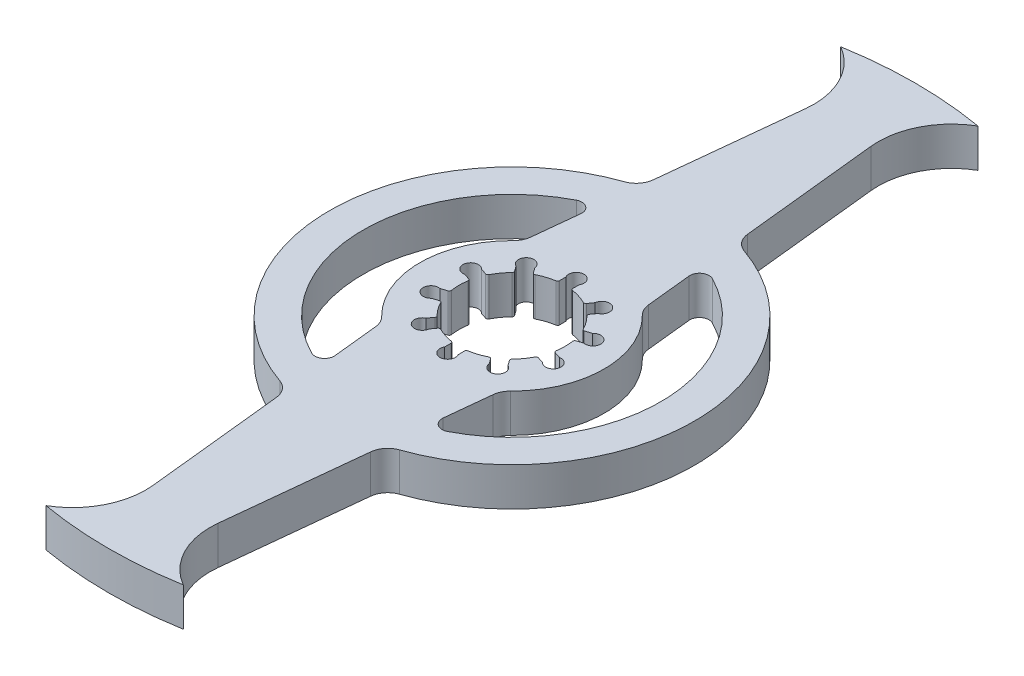
SolidWorks part; units mm, degrees
material "AISI Type A2 Tool Steel"
ref_plane "Front Plane" through (0, 0, 0) normal (0, 0, 1) x (1, 0, 0)
ref_plane "Top Plane" through (0, 0, 0) normal (0, 1, 0) x (1, 0, 0)
ref_plane "Right Plane" through (0, 0, 0) normal (1, 0, 0) x (0, 0, -1)
other "Center of Mass"
other "Bounding Box"
ref_plane "Default Plane" through (0, 2.286, 19.05) normal (0, -1, 0) x (-1, 0, 0)
sketch "Sketch1" plane through (0, 0, 0) normal (0, 1, 0) x (1, 0, 0)
  circle A0 centre (0, 0) radius 133.35 construction
  circle A1 centre (0, 0) radius 30.48
  circle A2 centre (0, 0) radius 17.4625
  dimension "D1" = 266.7
  dimension "D2" = 60.96
  dimension "D3" = 34.925
extrude "Boss-Extrude1" add sketch "Sketch1" along normal mid plane 12.7
sketch "Sketch2" plane through (0, 6.35, 0) normal (0, 1, 0) x (1, 0, 0)
  line L0 (-10.795, 107.95) -> (-19.6961, 23.2614)
  line L1 (19.6961, 23.2614) -> (10.795, 107.95)
  line L4 (0, 0) -> (0, 133.35) construction
  line L5 (-10.795, 107.95) -> (0, 107.95) construction
  line L6 (0, 107.95) -> (10.795, 107.95) construction
  line L7 (-22.6939, 131.4048) -> (0, 0) construction
  line L8 (-22.6939, 131.4048) -> (125.4677, 45.1673) construction
  circle A0 centre (0, 0) radius 133.35 construction
  circle A1 centre (0, 0) radius 133.35 construction
  arc A2 (-22.6939, 131.4048) -> (22.6939, 131.4048) centre (0, 0) cw
  arc A3 (-22.6939, 131.4048) -> (-10.795, 107.95) centre (-34.8727, 110.4807) cw
  circle A5 centre (0, 0) radius 30.48
  arc A6 (19.6961, 23.2614) -> (-19.6961, 23.2614) centre (0, 0) ccw
  arc A7 (-19.6961, 23.2614) -> (19.6961, 23.2614) centre (0, 0) ccw construction
  arc A8 (10.795, 107.95) -> (22.6939, 131.4048) centre (34.8727, 110.4807) cw
  dimension "D4" = 25.4
  dimension "D5" = 6
  dimension "D6" = 10.795
  dimension "D1" = 50
  dimension "D2" = 0
extrude "Boss-Extrude2" add sketch "Sketch2" against normal through all
sketch "Sketch5" plane through (0, 6.35, 0) normal (0, 1, 0) x (1, 0, 0)
  line L0 (0, 17.4625) -> (0, 21.2725) construction
  line L2 (-2.2225, 17.3205) -> (2.2225, 17.3205)
  line L3 (-2.2225, 17.3205) -> (-2.2225, 20.0168)
  line L5 (2.2225, 17.3205) -> (2.2225, 20.0168)
  arc A0 (2.2225, 20.0168) -> (-2.2225, 20.0168) centre (0, 21.2725) ccw
  circle A1 centre (0, 0) radius 17.4625 construction
  circle A2 centre (0, 21.2725) radius 4.5847 construction
  dimension "D2" = 5.1054
  dimension "D4" = 9.1694
  dimension "D1" = 3.81
  dimension "D3" = 4.445
extrude "Cut-Extrude2" cut sketch "Sketch5" against normal through all
pattern_circular "CirPattern1" count 10 over 360 about axis through (0, 6.35, 0) along (0, -1, 0) of "Cut-Extrude2"
sketch "Sketch6" plane through (0, 6.35, 0) normal (0, 1, 0) x (1, 0, 0)
  circle A0 centre (0, 0) radius 17.526
  arc A1 (-11.9788, 12.7062) -> (-15.786, 7.466) centre (0, 0) ccw construction
  dimension "D1" = 0.0635
extrude "Cut-Extrude3" cut sketch "Sketch6" against normal through all
sketch "Sketch8" plane through (0, 6.35, 0) normal (0, 1, 0) x (1, 0, 0)
  circle A0 centre (0, 0) radius 49.2125
  circle A1 centre (0, 0) radius 60.325
  dimension "D1" = 98.425
  dimension "D2" = 120.65
extrude "Boss-Extrude4" add sketch "Sketch8" against normal through all
sketch "Sketch11" plane through (0, 6.35, 0) normal (0, 1, 0) x (1, 0, 0)
  line L0 (-7.5441, 29.5316) -> (-5.5081, 48.9033)
  line L1 (5.5081, 48.9033) -> (7.5441, 29.5316)
  line L3 (-17.2986, 46.072) -> (-19.6961, 23.2614) construction
  line L4 (19.6961, 23.2614) -> (17.2986, 46.072) construction
  line L5 (-6.5261, 39.2174) -> (-17.8935, 40.4122) construction
  line L6 (6.5261, 39.2174) -> (17.8935, 40.4122) construction
  arc A0 (-7.5441, 29.5316) -> (7.5441, 29.5316) centre (0, 0) cw
  arc A1 (-5.5081, 48.9033) -> (5.5081, 48.9033) centre (0, 0) cw
  arc A2 (-19.6961, 23.2614) -> (19.6961, 23.2614) centre (0, 0) ccw construction
  arc A3 (-17.2986, 46.072) -> (17.2986, 46.072) centre (0, 0) ccw construction
  dimension "D1" = 11.43
extrude "Cut-Extrude6" [suppressed] cut sketch "Sketch11" against normal through all
fillet "Fillet6" radius 0.635 20 edges at (-12.0164, 0, -12.758) (-15.8469, 0, -7.4858) (-17.2204, 0, -3.2584) (-17.2204, 0, 3.2584) (-15.8469, 0, 7.4858) (-12.0164, 0, 12.758) (-8.4203, 0, 15.3707) (-2.2225, 0, 17.3845) (2.2225, 0, 17.3845) (8.4203, 0, 15.3707) (12.0164, 0, 12.758) (15.8469, 0, 7.4858) (17.2204, 0, 3.2584) (17.2204, 0, -3.2584) (15.8469, 0, -7.4858) (12.0164, 0, -12.758) (8.4203, 0, -15.3707) (2.2225, 0, -17.3845) (-2.2225, 0, -17.3845) (-8.4203, 0, -15.3707)
fillet "Fillet9" [suppressed] radius 3.175
mirror "Mirror1" about plane through (0, 0, 0) normal (0, 0, 1) of "Boss-Extrude2"
fillet "Fillet10" radius 6.35 8 edges at (-19.6961, 0, -23.2614) (-19.6961, 0, 23.2614) (19.6961, 0, 23.2614) (19.6961, 0, -23.2614) (-16.0285, 0, 58.1566) (16.0285, 0, 58.1566) (-16.0285, 0, -58.1566) (16.0285, 0, -58.1566)
fillet "Fillet11" radius 3.175 4 edges at (-17.2986, 0, 46.072) (17.2986, 0, 46.072) (17.2986, 0, -46.072) (-17.2986, 0, -46.072)
equation "\"Unit Measure\"= \"BoundingVolume\" / \"Thickness\"'in^2"
